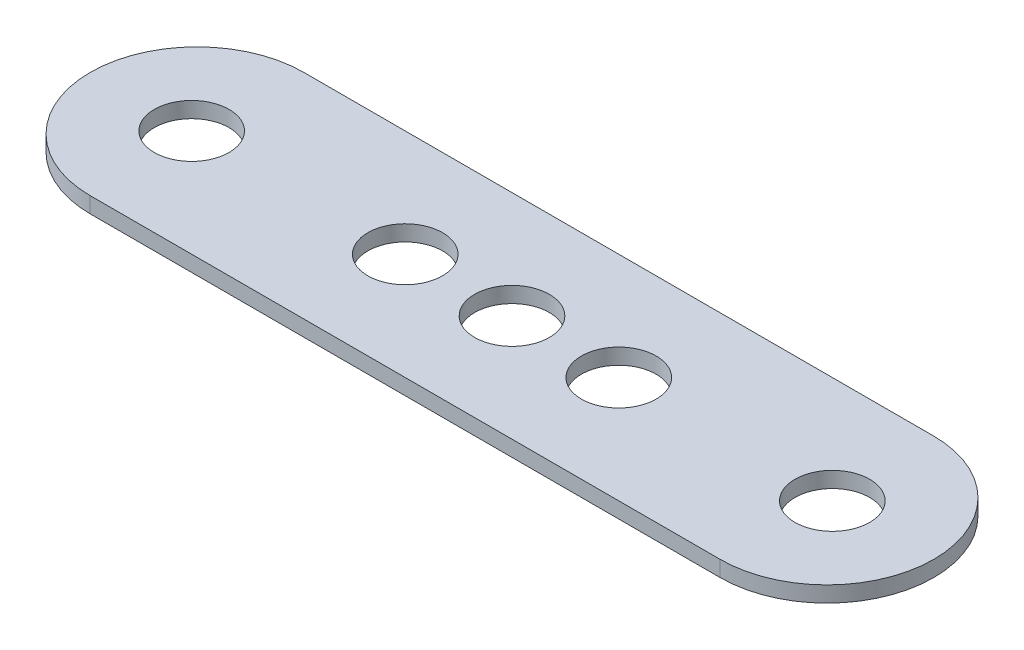
SolidWorks part; units mm, degrees
note: '?' marks a value the reader was unsure of.
ref_plane "Front Plane" through (0, 0, 0) normal (0, 0, 1) x (1, 0, 0)
ref_plane "Top Plane" through (0, 0, 0) normal (0, 1, 0) x (1, 0, 0)
ref_plane "Right Plane" through (0, 0, 0) normal (1, 0, 0) x (0, 0, -1)
ref_plane "Plane1"
sketch "Sketch1" plane through (0, 0, 0) normal (0, 1, 0) x (-1, 0, 0)
  line L0 (37.465, 6.35) -> (0, 6.35)
  line L1 (0, -6.35) -> (37.465, -6.35)
  arc A0 (37.465, -6.35) -> (37.465, 6.35) centre (37.465, 0) ccw
  arc A1 (0, 6.35) -> (0, -6.35) centre (0, 0) ccw
  circle A2 centre (-0.3175, 0) radius 2.2225
  circle A3 centre (37.7825, 0) radius 2.2225
  dimension "D1" = 12.7
  dimension "D3" = 4.445
  dimension "D2" = 37.465
  dimension "D4" = 38.1
extrude "Bar" add sketch "Sketch1" along normal blind 0.9398 contours L0 A1 L1 A0 A3 A2
ref_plane "Plane2" through (0, 0.9398, 0) normal (0, 1, 0) x (1, 0, 0)
sketch "Sketch2" plane through (0, 0.9398, 0) normal (0, 1, 0) x (1, 0, 0)
  circle A0 centre (-25.0825, 0) radius 2.2225
  dimension "D1" = 12.7
extrude "Center Hole" cut sketch "Sketch2" against normal through all
ref_plane "Plane3" through (0, 0, 0) normal (0, -1, 0) x (-1, 0, 0)
ref_plane "Plane4" through (0, 0, 0) normal (0, 0, 1) x (1, 0, 0)
ref_axis "Axis1" through (-80.9, 0, 0) along (1, 0, 0)?
pattern_linear "Other Center Holes" count 3 spacing 6.35 along (1, 0, 0) of "Center Hole"
